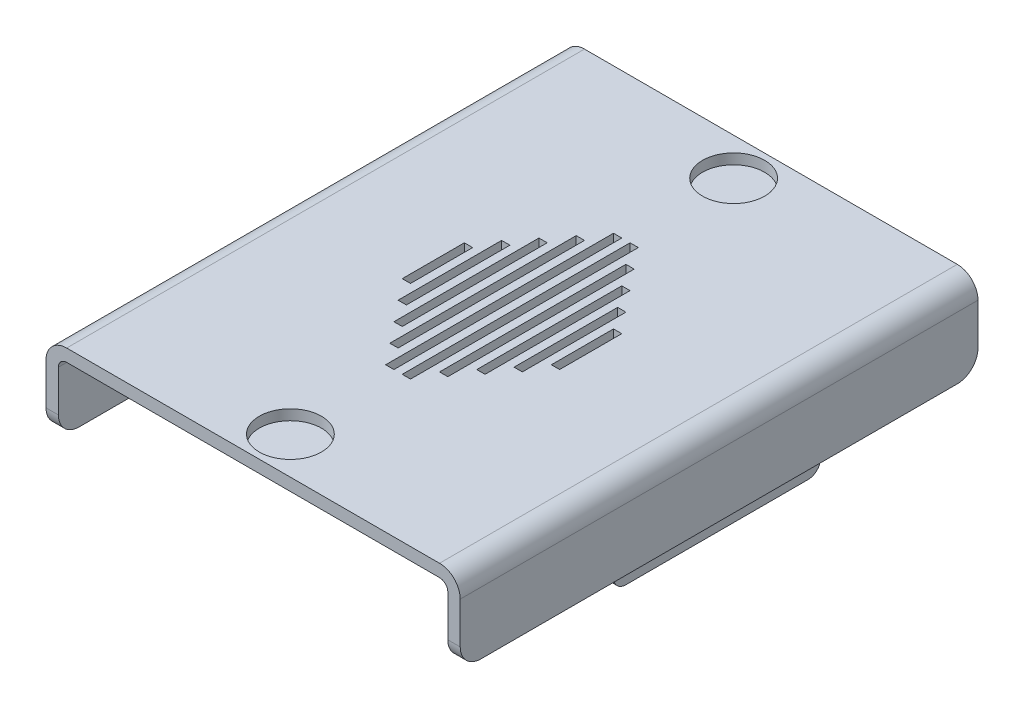
SolidWorks part; units mm, degrees
material "ABS"
ref_plane "Front Plane" through (0, 0, 0) normal (0, 0, 1) x (1, 0, 0)
ref_plane "Top Plane" through (0, 0, 0) normal (0, 1, 0) x (1, 0, 0)
ref_plane "Right Plane" through (0, 0, 0) normal (1, 0, 0) x (0, 0, -1)
sketch "Sketch1" plane through (0, 0, 0) normal (0, 0, 1) x (1, 0, 0)
  line L0 (-62.3906, 20.6479) -> (-62.3906, 26.5485) construction
  line L1 (-62.3906, 20.6479) -> (-62.3906, -14.3521) construction
  line L2 (-15.3906, 5.6479) -> (-15.3906, 20.6479)
  line L4 (-17.3906, 22.6479) -> (-107.3906, 22.6479)
  line L5 (-109.3906, 20.6479) -> (-109.3906, 5.6479)
  line L6 (-109.3906, 5.6479) -> (-112.3906, 5.6479)
  line L7 (-15.3906, 5.6479) -> (-12.3906, 5.6479)
  line L16 (-17.3906, 25.6479) -> (-107.3906, 25.6479)
  line L17 (-112.3906, 20.6479) -> (-112.3906, 5.6479)
  line L23 (-12.3906, 5.6479) -> (-12.3906, 20.6479)
  arc A0 (-107.3906, 25.6479) -> (-112.3906, 20.6479) centre (-107.3906, 20.6479) ccw
  arc A1 (-17.3906, 25.6479) -> (-12.3906, 20.6479) centre (-17.3906, 20.6479) cw
  arc A2 (-17.3906, 22.6479) -> (-15.3906, 20.6479) centre (-17.3906, 20.6479) cw
  arc A3 (-107.3906, 22.6479) -> (-109.3906, 20.6479) centre (-107.3906, 20.6479) ccw
  dimension "D4" = 20
  dimension "D5" = 100
  dimension "D1" = 5
  dimension "D2" = 3
  dimension "D3" = 20
extrude "Boss-Extrude1" add sketch "Sketch1" along normal blind 125
fillet "Fillet1" radius 5 4 edges at (-13.8906, 5.6479, 125) (-13.8906, 5.6479, 0) (-110.8906, 5.6479, 0) (-110.8906, 5.6479, 125)
sketch "Sketch2" plane through (0, 5.6479, 0) normal (0, -1, 0) x (1, 0, 0)
  line L1 (-107.3906, 35) -> (-110.3906, 35)
  line L2 (-107.3906, 35) -> (-107.3906, 85)
  line L3 (-107.3906, 85) -> (-110.3906, 85)
  line L4 (-110.3906, 35) -> (-110.3906, 85)
  line L6 (-82.3535, 85) -> (-109.3906, 85) construction
  line L7 (-109.3906, 120) -> (-109.3906, 5) construction
  line L9 (-12.3906, 35) -> (-12.3906, 85) construction
  line L10 (-15.3906, 85) -> (-12.3906, 85) construction
  line L11 (-15.3906, 35) -> (-15.3906, 85) construction
  line L12 (-15.3906, 35) -> (-12.3906, 35) construction
extrude "Boss-Extrude2" add sketch "Sketch2" against normal blind 18 and the other way blind 5
sketch "Sketch12" plane through (0, 5.6479, 0) normal (0, -1, 0) x (1, 0, 0)
  line L0 (-62.3906, 125) -> (-62.3906, 0) construction
  line L1 (-107.3906, 125) -> (-17.3906, 125) construction
  line L2 (-107.3906, 0) -> (-17.3906, 0) construction
  line L3 (-14.3906, 35) -> (-17.3906, 35)
  line L4 (-107.3906, 35) -> (-107.3906, 85)
  line L5 (-107.3906, 85) -> (-110.3906, 85)
  line L6 (-110.3906, 85) -> (-110.3906, 35)
  line L7 (-110.3906, 35) -> (-107.3906, 35)
  line L8 (-107.3906, 35) -> (-107.3906, 85) construction
  line L9 (-107.3906, 85) -> (-110.3906, 85) construction
  line L10 (-110.3906, 85) -> (-110.3906, 35) construction
  line L11 (-110.3906, 35) -> (-107.3906, 35) construction
  line L12 (-14.3906, 85) -> (-14.3906, 35)
  line L13 (-17.3906, 85) -> (-14.3906, 85)
  line L14 (-17.3906, 35) -> (-17.3906, 85)
  dimension "D1" = 0
extrude "Boss-Extrude5" add sketch "Sketch12" against normal blind 18 and the other way blind 5
sketch "Sketch3" plane through (0, 22.6479, 0) normal (0, -1, 0) x (1, 0, 0)
  line L0 (-62.3906, 0) -> (-62.3906, 120) construction
  line L1 (-42.3906, 10) -> (-82.3906, 10)
  line L2 (-42.3906, 10) -> (-42.3906, -5)
  line L3 (-42.3906, -5) -> (-82.3906, -5)
  line L4 (-82.3906, 10) -> (-82.3906, -5)
  line L5 (-62.3906, 125) -> (-62.3906, 127.9312) construction
  line L6 (-12.3906, 0) -> (-12.3906, 5) construction
  line L7 (-107.3906, 125) -> (-17.3906, 125) construction
  dimension "D1" = 20
  dimension "D2" = 40
  dimension "D3" = 15
  dimension "D4" = 50
extrude "Boss-Extrude3" add sketch "Sketch3" along normal blind 3
chamfer "Chamfer1" distance 4 angle 45 1 edges at (-62.3906, 22.6479, 10)
fillet "Fillet3" radius 4 2 edges at (-62.3906, 19.6479, 11) (-62.3906, 22.6479, 14)
fillet "Fillet4" radius 3 2 edges at (-82.3906, 21.1479, -5) (-42.3906, 21.1479, -5)
sketch "Sketch13" plane through (0, 25.6479, 0) normal (0, 1, 0) x (1, 0, 0)
  line L0 (-62.3906, 0) -> (-62.3906, -125) construction
  line L1 (-43.3906, -55) -> (-43.3906, -70)
  line L2 (-17.3906, -125) -> (-107.3906, -125) construction
  line L3 (-17.3906, 0) -> (-107.3906, 0) construction
  line L4 (-63.3906, -35) -> (-65.3906, -35)
  line L5 (-63.3906, -35) -> (-63.3906, -90)
  line L6 (-63.3906, -90) -> (-65.3906, -90)
  line L7 (-65.3906, -35) -> (-65.3906, -90)
  line L8 (-62.3906, -62.5) -> (-51.3906, -62.5) construction
  line L10 (-67.3906, -40) -> (-69.3906, -40)
  line L11 (-67.3906, -40) -> (-67.3906, -85)
  line L12 (-67.3906, -85) -> (-69.3906, -85)
  line L13 (-69.3906, -40) -> (-69.3906, -85)
  line L14 (-71.3906, -45) -> (-73.3906, -45)
  line L15 (-71.3906, -45) -> (-71.3906, -80)
  line L16 (-71.3906, -80) -> (-73.3906, -80)
  line L17 (-73.3906, -45) -> (-73.3906, -80)
  line L21 (-55.3906, -40) -> (-55.3906, -85)
  line L22 (-57.3906, -85) -> (-55.3906, -85)
  line L23 (-57.3906, -40) -> (-57.3906, -85)
  line L24 (-57.3906, -40) -> (-55.3906, -40)
  line L25 (-59.3906, -35) -> (-59.3906, -90)
  line L26 (-61.3906, -90) -> (-59.3906, -90)
  line L27 (-61.3906, -35) -> (-61.3906, -90)
  line L28 (-61.3906, -35) -> (-59.3906, -35)
  line L29 (-75.3906, -50) -> (-77.3906, -50)
  line L30 (-75.3906, -50) -> (-75.3906, -75)
  line L31 (-75.3906, -75) -> (-77.3906, -75)
  line L32 (-77.3906, -50) -> (-77.3906, -75)
  line L33 (-79.3906, -55) -> (-81.3906, -55)
  line L34 (-79.3906, -55) -> (-79.3906, -70)
  line L35 (-79.3906, -70) -> (-81.3906, -70)
  line L36 (-81.3906, -55) -> (-81.3906, -70)
  line L37 (-45.3906, -70) -> (-43.3906, -70)
  line L38 (-45.3906, -55) -> (-45.3906, -70)
  line L39 (-45.3906, -55) -> (-43.3906, -55)
  line L40 (-47.3906, -50) -> (-47.3906, -75)
  line L41 (-49.3906, -75) -> (-47.3906, -75)
  line L42 (-49.3906, -50) -> (-49.3906, -75)
  line L43 (-49.3906, -50) -> (-47.3906, -50)
  line L44 (-51.3906, -45) -> (-51.3906, -80)
  line L45 (-53.3906, -80) -> (-51.3906, -80)
  line L46 (-53.3906, -45) -> (-53.3906, -80)
  line L47 (-53.3906, -45) -> (-51.3906, -45)
extrude "Cut-Extrude1" cut sketch "Sketch13" against normal up to surface (3 mm away) up to face at (-62.3906, 22.6479, 43.4428)
fillet "Fillet5" radius 3 4 edges at (-108.8906, 0.6479, 85) (-108.8906, 0.6479, 35) (-15.8906, 0.6479, 35) (-15.8906, 0.6479, 85)
fillet "Fillet6" radius 3 2 edges at (-17.3906, 22.6479, 60) (-107.3906, 22.6479, 60)
sketch "Sketch14" plane through (0, 25.6479, 0) normal (0, 1, 0) x (1, 0, 0)
  line L0 (-112.3906, -62.5) -> (-12.3906, -62.5) construction
  line L1 (-112.3906, -125) -> (-112.3906, 0) construction
  line L5 (-12.3906, -125) -> (-12.3906, 0) construction
  circle A1 centre (-62.3906, -116) radius 7.5
  circle A2 centre (-62.3906, -9) radius 7.5
extrude "Cut-Extrude2" cut sketch "Sketch14" against normal blind 2.5
sketch "Sketch15" plane through (0, 22.6479, 0) normal (0, -1, 0) x (1, 0, 0)
  line L1 (-39.0075, 17.5717) -> (-86.0569, 17.5717)
  line L2 (-39.0075, 17.5717) -> (-39.0075, -7.9069)
  line L3 (-39.0075, -7.9069) -> (-86.0569, -7.9069)
  line L4 (-86.0569, 17.5717) -> (-86.0569, -7.9069)
  point P4 (-39.0075, 17.5717)
extrude "Cut-Extrude3" cut sketch "Sketch15" along normal up to surface (3 mm away) up to face at (-62.3906, 19.6479, 0.5739)
sketch "Sketch16" plane through (0, 0.6479, 0) normal (0, -1, 0) x (1, 0, 0)
  line L1 (-15.3906, 5) -> (-12.3906, 5)
  line L2 (-15.3906, 5) -> (-15.3906, 120)
  line L3 (-15.3906, 120) -> (-12.3906, 120)
  line L4 (-12.3906, 5) -> (-12.3906, 120)
  line L5 (-109.3906, 5) -> (-112.3906, 5)
  line L6 (-109.3906, 5) -> (-109.3906, 120)
  line L7 (-109.3906, 120) -> (-112.3906, 120)
  line L8 (-112.3906, 5) -> (-112.3906, 120)
extrude "Cut-Extrude4" cut sketch "Sketch16" against normal up to surface (5 mm away) up to face at (-14.3906, 5.6479, 61.25)
